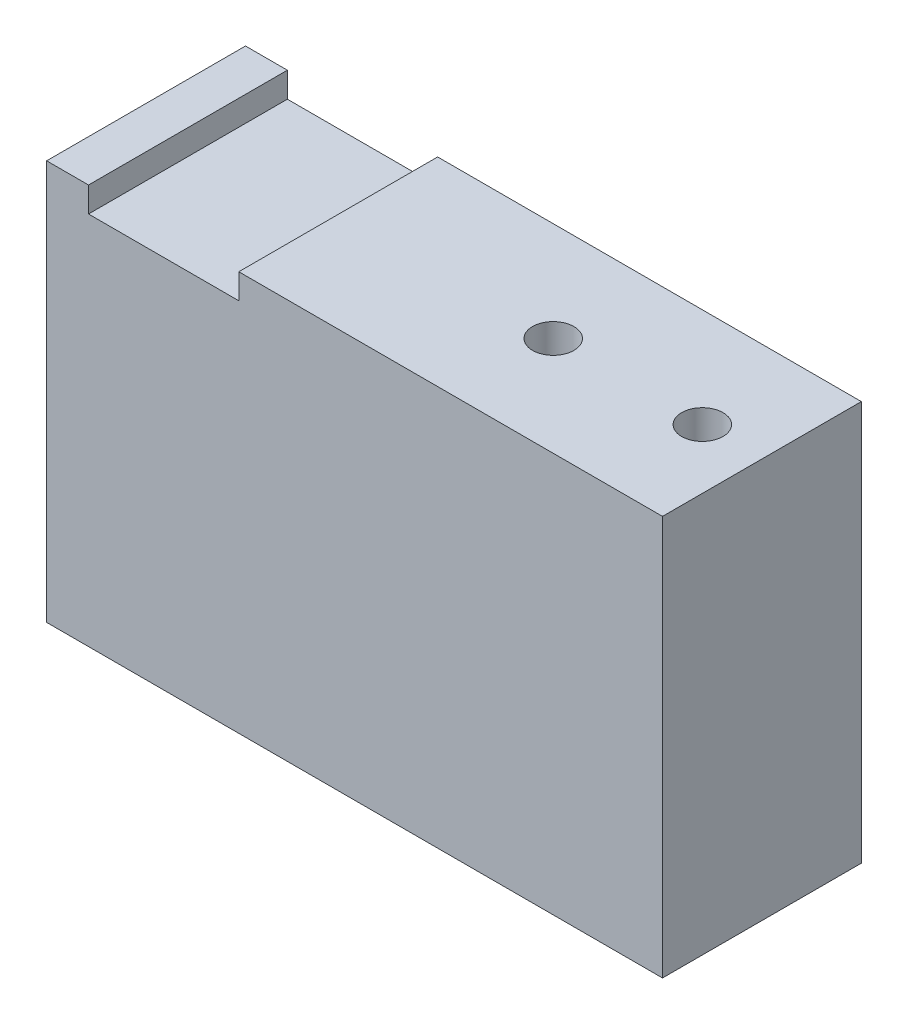
SolidWorks part; units mm, degrees
ref_plane "Спереди" through (0, 0, 0) normal (0, 0, 1) x (1, 0, 0)
ref_plane "Сверху" through (0, 0, 0) normal (0, 1, 0) x (1, 0, 0)
ref_plane "Справа" through (0, 0, 0) normal (1, 0, 0) x (0, 0, -1)
other "Configuration Table"
sketch "основание" plane through (0, 0, 0) normal (0, 1, 0) x (1, 0, 0)
  line L1 (-31.25, -10.09) -> (31.25, -10.09)
  line L2 (-31.25, -10.09) -> (-31.25, 10.09)
  line L3 (-31.25, 10.09) -> (31.25, 10.09)
  line L4 (31.25, -10.09) -> (31.25, 10.09)
  line L5 (-31.25, -10.09) -> (31.25, 10.09) construction
  line L6 (-31.25, 10.09) -> (31.25, -10.09) construction
  point P0 (0, 0)
  dimension "D1" = 20.18
  dimension "D2" = 62.5
extrude "Бобышка-Вытянуть1" add sketch "основание" along normal blind 40.57
sketch "Эскиз5" plane through (0, 40.57, 0) normal (0, 1, 0) x (1, 0, 0)
sketch "Эскиз6" plane through (0, 40.57, 0) normal (0, 1, 0) x (1, 0, 0)
  line L0 (31.25, 10.09) -> (-31.25, 10.09) construction
  line L1 (-27, 10.09) -> (-11.75, 10.09)
  line L2 (-27, 10.09) -> (-27, -10.09)
  line L3 (-27, -10.09) -> (-11.75, -10.09)
  line L4 (-11.75, 10.09) -> (-11.75, -10.09)
  line L5 (-31.25, -10.09) -> (31.25, -10.09) construction
  dimension "D1" = 15.25
  dimension "D2" = 4.25
extrude "Вырез-Вытянуть1" cut sketch "Эскиз6" against normal blind 2.55
sketch "Эскиз7" plane through (0, 40.57, 0) normal (0, 1, 0) x (1, 0, 0)
  line L0 (0, 0) -> (46.5539, 0) construction
  line L2 (31.25, -10.09) -> (31.25, 10.09) construction
  circle A0 centre (25.2, 0) radius 2.1
  circle A1 centre (10.07, 0) radius 2.1
  point P7 (27.3, 0)
  point P10 (12.17, 0)
  point P11 (23.1, 0)
  dimension "D1" = 4.2
  dimension "D2" = 4.2
  dimension "D3" = 3.95
  dimension "D4" = 10.93
extrude "Вырез-Вытянуть2" cut sketch "Эскиз7" against normal blind 15 contours L0 A0 | A0 L0 | A1 region at (25.2, 40.57, -0.8913) region at (25.2, 40.57, 0.8913)
sketch "Эскиз8" plane through (0, 0, 0) normal (0, -1, 0) x (1, 0, 0)
  line L0 (0, 0) -> (41.9235, 0) construction
  line L1 (0, 0) -> (0, 26.7891) construction
  circle A0 centre (17, 0) radius 2.5
  circle A1 centre (-17, 0) radius 2.5
  dimension "D1" = 5
  dimension "D2" = 17
extrude "Вырез-Вытянуть4" cut sketch "Эскиз8" against normal blind 15
